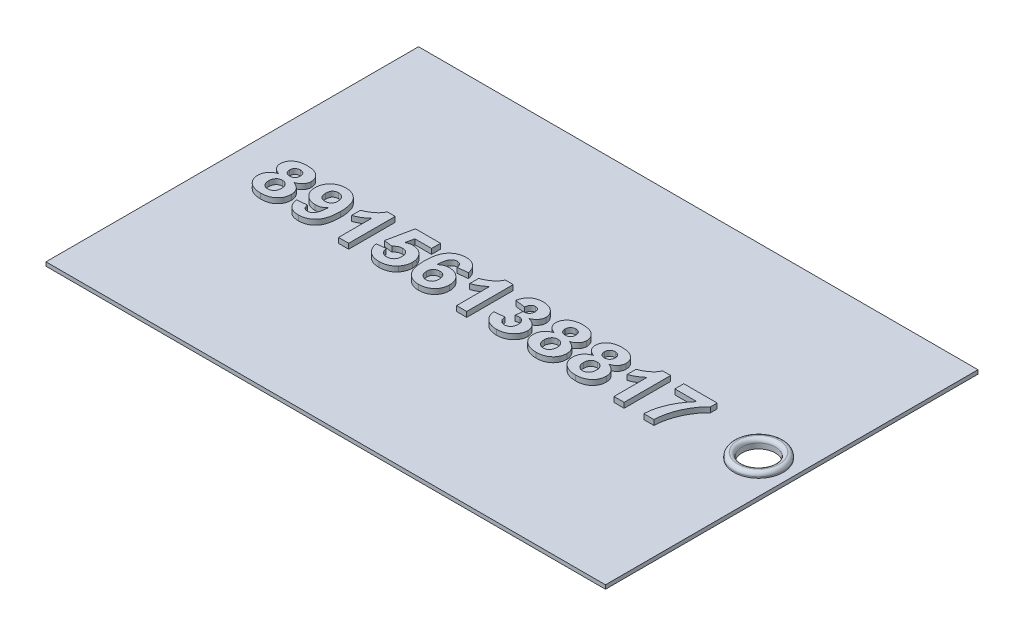
SolidWorks part; units mm, degrees
ref_plane "Спереди" through (0, 0, 0) normal (0, 0, 1) x (1, 0, 0)
ref_plane "Сверху" through (0, 0, 0) normal (0, 1, 0) x (1, 0, 0)
ref_plane "Справа" through (0, 0, 0) normal (1, 0, 0) x (0, 0, -1)
other "Configuration Table"
sketch "Эскиз1" plane through (0, 0, 0) normal (0, 1, 0) x (1, 0, 0)
  line L1 (-43.25, -28.8) -> (43.25, -28.8)
  line L2 (-43.25, -28.8) -> (-43.25, 28.8)
  line L3 (-43.25, 28.8) -> (43.25, 28.8)
  line L4 (43.25, -28.8) -> (43.25, 28.8)
  line L5 (0, 28.8) -> (0, -28.8) construction
  line L6 (-43.25, 0) -> (43.25, 0) construction
  point P0 (0, 0)
  dimension "D1" = 86.5
  dimension "D2" = 57.6
extrude "Бобышка-Вытянуть1" add sketch "Эскиз1" along normal blind 0.6
sketch "Эскиз2" plane through (0, 0.6, 0) normal (0, 1, 0) x (1, 0, 0)
  line L0 (-43.25, 0) -> (43.25, 0) construction
  line L1 (-43.25, 28.8) -> (-43.25, -28.8) construction
  line L2 (43.25, -28.8) -> (43.25, 28.8) construction
  line L3 (0, 28.8) -> (0, -28.8) construction
  line L4 (43.25, 28.8) -> (-43.25, 28.8) construction
  line L5 (-43.25, -28.8) -> (43.25, -28.8) construction
  text T0 "89156138817" font "Arial" height in points 28
extrude "Бобышка-Вытянуть2" add sketch "Эскиз2" along normal blind 0.8
sketch "Эскиз4" plane through (0, 0.6, 0) normal (0, 1, 0) x (1, 0, 0)
  line L0 (-43.25, 0) -> (43.25, 0) construction
  line L1 (-43.25, 28.8) -> (-43.25, -28.8) construction
  line L2 (43.25, -28.8) -> (43.25, 28.8) construction
  circle A0 centre (38.1303, 0) radius 3.8176
extrude "Бобышка-Вытянуть3" add sketch "Эскиз4" along normal blind 0.8
sketch "Эскиз6" plane through (0, 1.4, 0) normal (0, 1, 0) x (1, 0, 0)
  line L0 (38.1303, 3.8176) -> (38.1303, -3.8176) construction
  line L1 (34.3127, 0) -> (41.9478, 0) construction
  circle A0 centre (38.1303, 0) radius 3.8176 construction
  circle A1 centre (38.1303, 0) radius 3.8176 construction
  circle A2 centre (38.1303, 0) radius 2.579
extrude "Вырез-Вытянуть1" cut sketch "Эскиз6" against normal blind 1.8
fillet "Скругление1" radius 0.6 2 edges at (38.1303, 1.4, 3.8176) (38.1303, 1.4, 2.579)
